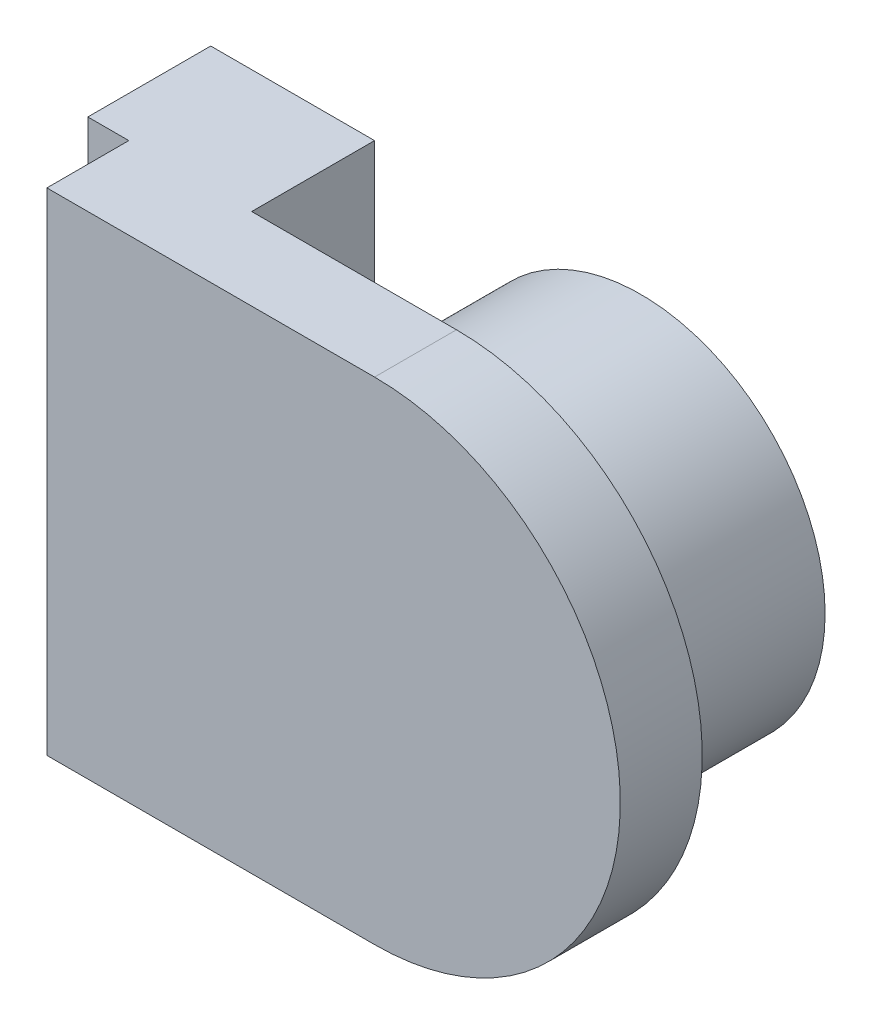
SolidWorks part; units mm, degrees
ref_plane "Front Plane" through (0, 0, 0) normal (0, 0, 1) x (1, 0, 0)
ref_plane "Top Plane" through (0, 0, 0) normal (0, 1, 0) x (1, 0, 0)
ref_plane "Right Plane" through (0, 0, 0) normal (1, 0, 0) x (0, 0, -1)
sketch "Sketch1" plane through (0, 0, 0) normal (0, 0, 1) x (1, 0, 0)
  line L1 (0, 0) -> (-8, 0)
  line L2 (0, 0) -> (0, 12)
  line L3 (0, 12) -> (-8, 12)
  line L4 (-8, 0) -> (-8, 12)
  arc A0 (0, 12) -> (0, 0) centre (0, 6) cw
  circle A1 centre (0, 6) radius 4.5
  circle A2 centre (0, 6) radius 0.5
  dimension "6" = 6
  dimension "D3" = 9
  dimension "D4" = 1
  dimension "D1" = 8
extrude "Boss-Extrude1" add sketch "Sketch1" along normal blind 2 contours A1 L2 L3 L4 L1 | A2 L2 A1 | A2 L2 A1 | A1 L2 A0 | A2 region at (-5.0357, 6, 0) region at (0.1342, 0.75, 0) region at (-1.9311, 6, 0) region at (1.9311, 6, 0)
extrude "Boss-Extrude2" add sketch "Sketch1<3>" against normal blind 4.5 separate body contours L2 A2 | L2 A2 | A2 L2 A1 | A2 L2 A1 region at (-1.9311, 6, 0) region at (1.9311, 6, 0) region at (-0.2122, 6, 0) region at (0.2122, 6, 0)
sketch "Sketch1<3>" plane through (0, 0, 0) normal (0, 0, 1) x (1, 0, 0) same geometry as "Sketch1"
extrude "Boss-Extrude3" add sketch "Sketch1<4>" against normal blind 5 contours L2 A2 | L2 A2 region at (-0.2122, 6, 0) region at (0.2122, 6, 0)
sketch "Sketch1<4>" plane through (0, 0, 0) normal (0, 0, 1) x (1, 0, 0) same geometry as "Sketch1"
sketch "Sketch3" plane through (0, 0, 0) normal (0, 0, -1) x (-1, 0, 0)
  line L0 (0, 0) -> (8, 0) construction
  line L1 (8, 12) -> (5, 12)
  line L2 (8, 12) -> (8, 0)
  line L3 (8, 0) -> (5, 0)
  line L4 (5, 12) -> (5, 0)
  line L6 (8, 12) -> (9, 12)
  line L7 (8, 12) -> (8, 0)
  line L8 (8, 0) -> (9, 0)
  line L9 (9, 12) -> (9, 0)
  line M4 (0, 0) -> (8, 0)
  line M5 (8, 0) -> (8, 12)
  line M6 (8, 12) -> (0, 12)
  dimension "D1" = 3
  dimension "D2" = 1
extrude "Boss-Extrude4" add sketch "Sketch3" along normal blind 3 contours L9 L6 L8 M5 | L4 M6 M4 M5 region at (-6.5, 6, 0) region at (-8.5, 6, 0)
